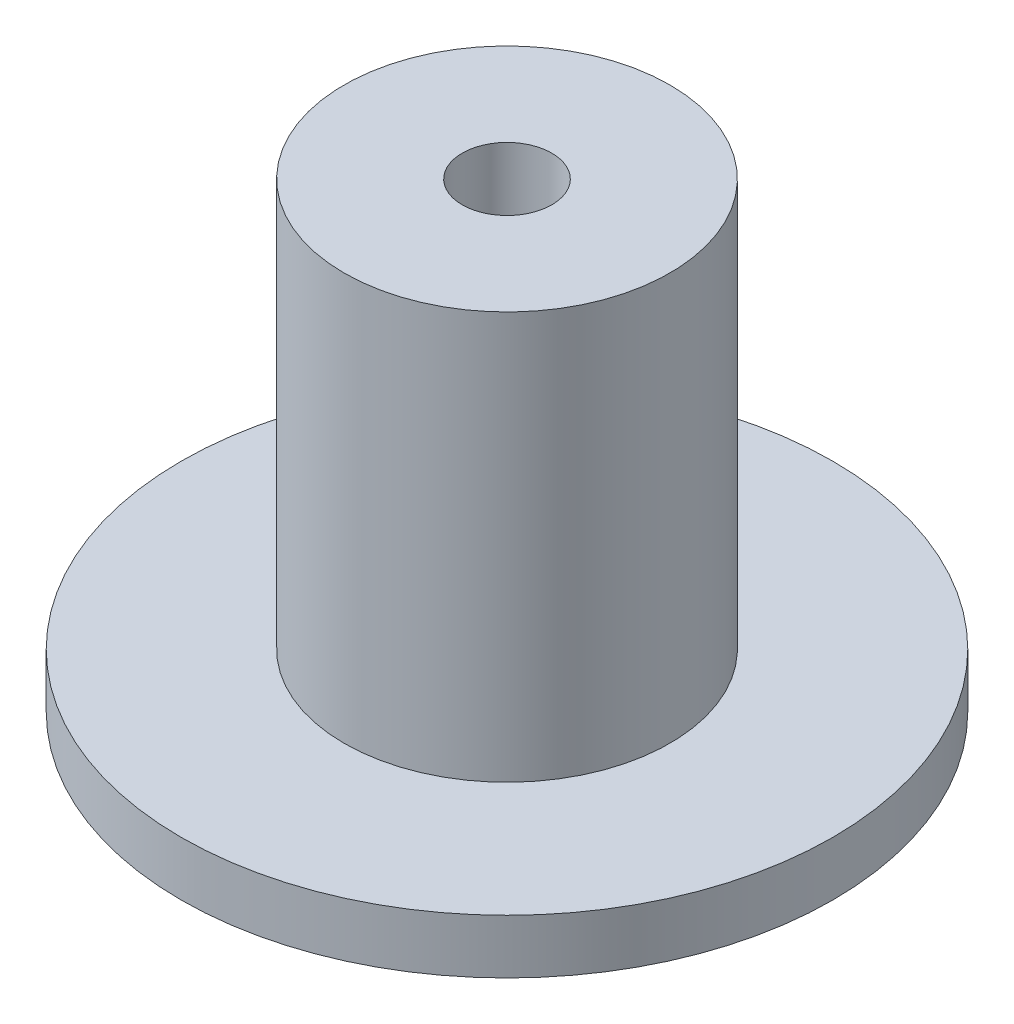
SolidWorks part; units mm, degrees
ref_plane "Front" through (0, 0, 0) normal (0, 0, 1) x (1, 0, 0)
ref_plane "Top" through (0, 0, 0) normal (0, 1, 0) x (1, 0, 0)
ref_plane "Right" through (0, 0, 0) normal (1, 0, 0) x (0, 0, -1)
ref_axis "X" through (-80.9, 0, 0) along (1, 0, 0)
ref_axis "Y" through (0, -50, 0) along (0, 1, 0)
ref_axis "Z" through (0, 0, -80.9) along (0, 0, 1)
sketch "Sketch1" plane through (0, 0, 0) normal (0, 0, 1) x (1, 0, 0)
  line L0 (0, 0) -> (-2, 0)
  line L1 (-12, 2) -> (-12, 4)
  line L2 (-12, 4) -> (-6, 4)
  line L3 (0, 19) -> (0, 0)
  line L4 (0, -1.7854) -> (0, -0.4404) construction
  line L5 (-6, 4) -> (-6, 19)
  line L6 (-6, 19) -> (0, 19)
  arc A0 (-2, 0) -> (-12, 2) centre (-2, 26) cw
  point P7 (0, 13.8018)
  dimension "D3" = 2
  dimension "D1" = 4
  dimension "D2" = 24
  dimension "D4" = 2
  dimension "D5" = 12
  dimension "D6" = 19
revolve "Revolve1" add sketch "Sketch1" angle 360 about L4
hole_wizard "M4x0.7 Tapped Hole1" positions "Sketch2" profile "Sketch4" tap size "M4x0.7" standard "ANSI Metric"
sketch "Sketch2" plane through (0, 19, 0) normal (0, 1, 0) x (1, 0, 0)
  point P0 (0, 0)
sketch "Sketch4" plane through (0, 19, 0) normal (1, 0, 0) x (0, 0, 1)
  line L0 (0, 0) -> (0, 11.0914)
  line L1 (0, 11.0914) -> (1.65, 10.1)
  line L2 (1.65, 10.1) -> (1.65, 0)
  line L5 (1.65, 0) -> (0, 0)
  line L10 (0, 11.0914) -> (-1.65, 10.1) construction
  line L11 (0, -6.35) -> (0, 107.95) construction
  dimension "Tap Drill Dia." = 3.3
  dimension "Tap Drill Depth" = 10.1
  dimension "Drill Angle" = 118
cosmetic thread "Hole Thread1" parameters "D1"=8, "D2"=4
